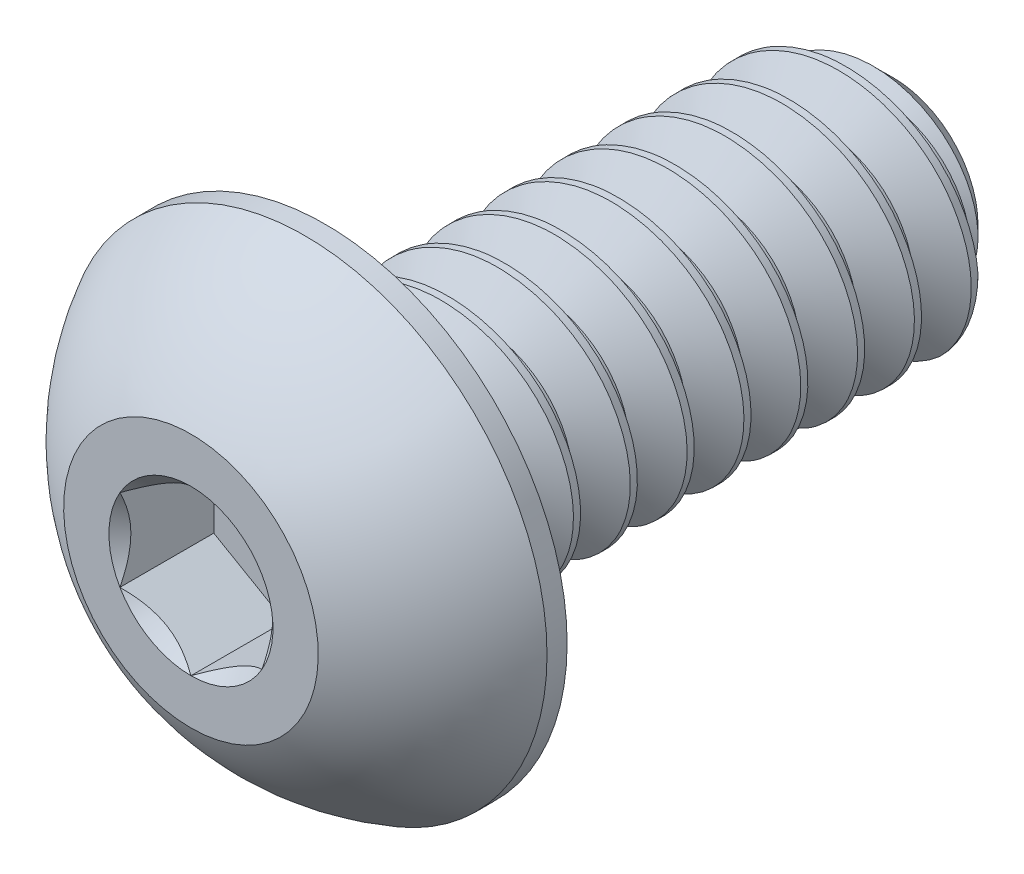
SolidWorks part; units mm, degrees
ref_plane "Front" through (0, 0, 0) normal (0, 0, 1) x (1, 0, 0)
ref_plane "Top" through (0, 0, 0) normal (0, 1, 0) x (1, 0, 0)
ref_plane "Right" through (0, 0, 0) normal (1, 0, 0) x (0, 0, -1)
sketch "Sketch1" plane through (0, 0, 0) normal (1, 0, 0) x (0, 0, -1)
  line L2 (1.4986, 1.4224) -> (7.8486, 1.4224)
  line L3 (7.8486, 1.4224) -> (7.8486, 0)
  line L4 (7.8486, 0) -> (1.4986, 0)
  line L6 (1.2738, 2.7051) -> (1.4986, 2.7051) construction
  line L7 (7.8486, 1.4224) -> (7.8486, -1.4224) construction
  line L8 (0, 0) -> (1.4986, 0) construction
  line L9 (1.4986, 2.7051) -> (1.4986, -2.7051) construction
  line L11 (1.4986, 1.4224) -> (1.4986, 0)
  line L13 (0, 0.7937) -> (0, -0.7937) construction
  line L14 (0, 0.7937) -> (0, 1.4224) construction
  arc A3 (0, 1.4224) -> (1.2738, 2.7051) centre (2.7151, 0) cw construction
  dimension "D1" = 0.2248
revolve "Revolve1" add sketch "Sketch1" angle 360 mid plane about L4
sketch "Sketch3" plane through (0, 0, -7.8486) normal (0, 0, -1) x (-1, 0, 0)
  circle A0 centre (0, 0) radius 1.4224
curve "Helix/Spiral1" pitch 0.635 height 6.985 radius 1.4224 centre (0, 0, -7.8486) axis (0, 0, 1) start towards (0, 1, 0)
sketch "Sketch2" plane through (0, 0, 0) normal (1, 0, 0) x (0, 0, -1)
  line L0 (7.8486, 1.4224) -> (8.4042, 1.4224)
  line L1 (8.4042, 1.4224) -> (8.1661, 1.01)
  line L2 (8.1661, 1.01) -> (8.0867, 1.01)
  line L3 (8.0867, 1.01) -> (7.8486, 1.4224)
  line L4 (7.9677, 1.2162) -> (8.2852, 1.2162) construction
  dimension "D1" = 60
  dimension "D2" = 0.0794
  dimension "D3" = 0.3175
chamfer "Chamfer1" distance 0.4763 angle 45 1 edges at (0, 1.4224, -7.8486)
sweep "Cut-Sweep1" cut profiles "Sketch2" path "Helix/Spiral1" align with end faces yes
sketch "Sketch7" plane through (0, 0, 0) normal (1, 0, 0) x (0, 0, -1)
  line L6 (1.2738, 2.7051) -> (1.4986, 2.7051) construction
  line L8 (0, 0) -> (1.4986, 0) construction
  line L11 (1.4986, 2.7051) -> (1.4986, -2.7051) construction
  line L12 (1.2738, 2.7051) -> (1.4986, 2.7051)
  line L13 (0, 0) -> (1.4986, 0)
  line L14 (0, 0.7937) -> (0, -0.7937) construction
  line L15 (1.4986, 2.7051) -> (1.4986, 0)
  line L16 (0, 1.4224) -> (0, 0)
  arc A2 (1.2738, 2.7051) -> (0, 1.4224) centre (2.7151, 0) ccw construction
  arc A3 (1.2738, 2.7051) -> (0, 1.4224) centre (2.7151, 0) ccw
revolve "Revolve2" add sketch "Sketch7" angle 360 mid plane about L13
sketch "Sketch5" plane through (0, 0, 0) normal (0, 0, 1) x (1, 0, 0)
  line L1 (0.7937, -0.4583) -> (0.7937, 0.4583)
  line L2 (0.7937, 0.4583) -> (0, 0.9165)
  line L3 (0, 0.9165) -> (-0.7937, 0.4583)
  line L4 (-0.7937, 0.4583) -> (-0.7937, -0.4583)
  line L5 (-0.7937, -0.4583) -> (0, -0.9165)
  line L6 (0, -0.9165) -> (0.7937, -0.4583)
  circle A0 centre (0, 0) radius 0.7937 construction
extrude "Cut-Extrude2" cut sketch "Sketch5" against normal blind 1.049
sketch "Sketch6" plane through (0, 0, 0) normal (0, 0, 1) x (1, 0, 0)
  circle A0 centre (0, 0) radius 0.9165
extrude "Cut-Extrude3" cut sketch "Sketch6" against normal blind 1.049 draft 45
sketch "Sketch9" [suppressed] plane through (0, 0, -1.4986) normal (0, 0, 1) x (1, 0, 0)
  circle A2 centre (0, 0) radius 1.4224
extrude "Boss-Extrude2" [suppressed] add sketch "Sketch9" against normal offset from surface (12.7 mm away) 31.75 up to face at (0, 0.9461, -7.8486)
equation "\"D3@Helix/Spiral1\" = \"Lg@Sketch1\" + \"D4@Helix/Spiral1\""
equation "\"D2@Sketch2\" = \"D4@Helix/Spiral1\" * .125"
equation "\"D3@Sketch2\" = \"D4@Helix/Spiral1\" * .5"
equation "\"D1@Chamfer1\" = \"D4@Helix/Spiral1\" * .75"
equation "\"D1@Cut-Extrude2\" = \"Head Ht@Sketch1\" * .7"
equation "\"D1@Sketch1\" = \"Head Ht@Sketch1\" * .15"
equation "\"D1@Cut-Extrude3\" = \"D1@Cut-Extrude2\""
